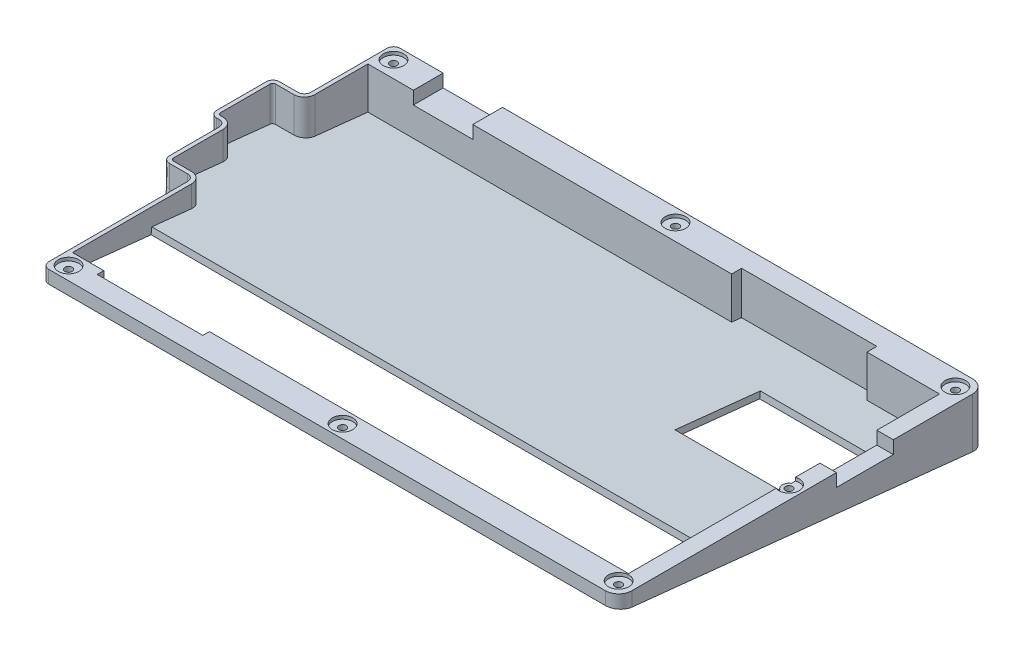
SolidWorks part; units mm, degrees
ref_plane "Front Plane" through (0, 0, 0) normal (0, 0, 1) x (1, 0, 0)
ref_plane "Top Plane" through (0, 0, 0) normal (0, 1, 0) x (1, 0, 0)
ref_plane "Right Plane" through (0, 0, 0) normal (1, 0, 0) x (0, 0, -1)
sketch "Sketch1" plane through (0, 0, 0) normal (0, 1, 0) x (1, 0, 0)
  line L0 (138.4196, 31.7518) -> (125.4196, 31.7518)
  line L1 (-35.0204, 31.7518) -> (107.4196, 31.7518)
  line L2 (140.4196, 29.7518) -> (140.4196, 6.7018)
  line L3 (-34.0204, 3.7518) -> (-34.0204, 22.7518)
  line L4 (136.4596, 27.7518) -> (136.4396, 27.7518)
  line L5 (142.4196, 4.7018) -> (147.9496, 4.7018)
  line L6 (-34.0204, 22.7518) -> (-12.0204, 22.7518)
  line L8 (149.9496, 2.7018) -> (149.9496, -12.3482)
  line L11 (147.9496, -14.3482) -> (147.1896, -14.3482)
  line L14 (145.1896, -16.3482) -> (145.1896, -31.3982)
  line L17 (143.1896, -33.3982) -> (137.6696, -33.3982)
  line L20 (135.6696, -35.3982) -> (135.6696, -77.4982)
  line L21 (-34.0204, -25.6003) -> (-34.0204, -71.4982)
  line L23 (133.6696, -79.4982) -> (-35.0204, -79.4982)
  line L28 (-39.0204, 27.7518) -> (-39.0204, 3.7518)
  line L31 (-34.0204, 3.7518) -> (-39.0204, 3.7518)
  line L32 (-34.0204, -13.4982) -> (-39.0204, -13.4982)
  line L33 (-39.0204, -75.4982) -> (-39.0204, -13.4982)
  line L34 (-34.0204, -71.4982) -> (92.9796, -71.4982)
  line L35 (92.9796, -71.4982) -> (92.9796, -73.4982)
  line L36 (92.9796, -73.4982) -> (124.9796, -73.4982)
  line L37 (124.9796, -73.4982) -> (124.9796, -71.4982)
  line L39 (134.4706, -35.3982) -> (134.4706, -71.4982)
  line L40 (134.4706, -71.4982) -> (124.9796, -71.4982)
  line L41 (137.6696, -32.1992) -> (143.1896, -32.1992)
  line L42 (-34.0204, -13.4982) -> (-34.0204, -22.1362)
  line L43 (143.9906, -31.3982) -> (143.9906, -16.3482)
  line L44 (-12.0204, 22.7518) -> (-12.0204, 25.7518)
  line L45 (147.1896, -13.1492) -> (147.9496, -13.1492)
  line L46 (148.7506, -12.3482) -> (148.7506, 2.7018)
  line L47 (-12.0204, 25.7518) -> (28.9796, 25.7518)
  line L48 (28.9796, 25.7518) -> (28.9796, 22.7518)
  line L49 (28.9796, 22.7518) -> (107.4196, 22.7518)
  line L50 (147.9496, 3.5027) -> (142.4196, 3.5027)
  line L51 (107.4196, 22.7518) -> (107.4196, 31.7518)
  line L52 (139.2206, 6.7018) -> (139.2206, 22.7518)
  line L53 (125.4196, 31.7518) -> (125.4196, 22.7518)
  line L54 (139.2206, 22.7518) -> (125.4196, 22.7518)
  arc A0 (138.4196, 31.7518) -> (140.4196, 29.7518) centre (138.4196, 29.7518) cw
  arc A1 (140.4196, 6.7018) -> (142.4196, 4.7018) centre (142.4196, 6.7018) ccw
  arc A2 (149.9496, 2.7018) -> (147.9496, 4.7018) centre (147.9496, 2.7018) ccw
  arc A3 (149.9496, -12.3482) -> (147.9496, -14.3482) centre (147.9496, -12.3482) cw
  arc A4 (147.1896, -14.3482) -> (145.1896, -16.3482) centre (147.1896, -16.3482) ccw
  arc A5 (145.1896, -31.3982) -> (143.1896, -33.3982) centre (143.1896, -31.3982) cw
  arc A6 (-35.0204, 31.7518) -> (-39.0204, 27.7518) centre (-35.0204, 27.7518) ccw
  arc A7 (-39.0204, -75.4982) -> (-35.0204, -79.4982) centre (-35.0204, -75.4982) ccw
  arc A8 (133.6696, -79.4982) -> (135.6696, -77.4982) centre (133.6696, -77.4982) ccw
  arc A9 (135.6696, -35.3982) -> (137.6696, -33.3982) centre (137.6696, -35.3982) cw
  circle A10 centre (-34.4204, 27.1518) radius 1.1
  circle A11 centre (51.0096, 27.7518) radius 1.1
  circle A12 centre (136.4396, 27.7518) radius 1.1
  circle A13 centre (-34.4204, -74.8982) radius 1.1
  circle A14 centre (48.6296, -75.4982) radius 1.1
  circle A15 centre (131.6496, -75.4982) radius 1.1
  circle A16 centre (-35.0204, -23.8682) radius 1.1
  arc A27 (-34.0204, -22.1362) -> (-34.0204, -25.6003) centre (-35.0204, -23.8682) cw
  arc A28 (139.2206, 6.7018) -> (142.4196, 3.5027) centre (142.4196, 6.7018) ccw
  arc A29 (147.9496, 3.5027) -> (148.7506, 2.7018) centre (147.9496, 2.7018) cw
  arc A30 (148.7506, -12.3482) -> (147.9496, -13.1492) centre (147.9496, -12.3482) cw
  arc A31 (147.1896, -13.1492) -> (143.9906, -16.3482) centre (147.1896, -16.3482) ccw
  arc A32 (143.9906, -31.3982) -> (143.1896, -32.1992) centre (143.1896, -31.3982) cw
  arc A33 (137.6696, -32.1992) -> (134.4706, -35.3982) centre (137.6696, -35.3982) ccw
extrude "Boss-Extrude2" add sketch "Sketch1" against normal blind 4.7 contours L41 A33 L39 L40 L37 L36 L35 L34 L21 A27 L42 L32 L33 A7 L23 A8 L20 A9 L17 A5 L14 A4 L11 A3 L8 A2 L5 A1 L2 A0 L0 L53 L54 L52 A28 L50 A29 L46 A30 L45 A31 L43 A32 A12 A13 A14 A15 | L1 A6 L28 L31 L3 L6 L44 L47 L48 L49 L51 A11 A10 region at (138.2833, 0, -29.6154) region at (31.7683, 0, -26.4895)
move or copy body "Body-Move/Copy1" bodies to move or copy 105 104 copy no rotation origin (55.4646, -2.35, 0) rotation axis (0, 0, 1) rotation angle 180
sketch "Sketch3" plane through (149.9496, 0, 0) normal (1, 0, 0) x (0, 0, -1)
  line L0 (-79.4982, 0) -> (-79.4982, -4.7) construction
  line L1 (-79.4982, 0) -> (-79.4982, -4.7)
  line L2 (31.7518, 0) -> (31.7518, -4.7) construction
  line L3 (31.7518, 0) -> (31.7518, -4.7)
  line L5 (-79.4982, -4.7) -> (31.7518, -16.3928)
  line L6 (31.7518, -16.3928) -> (31.7518, -4.7)
  line L7 (31.7518, -4.7) -> (-79.4982, -4.7)
  line M3 (-75.4982, -4.7) -> (-13.4982, -4.7)
  dimension "D1" = 6
extrude "Boss-Extrude3" add sketch "Sketch3" against normal up to surface (188.97 mm away) contours L6 L7 L5 M3 region at (149.9496, -8.5976, 5.3315) up to face at (-39.0204, -2.35, 4.8232)
sketch "Sketch4" plane through (0, -4.7, 0) normal (0, 1, 0) x (1, 0, 0)
  line L2 (145.9496, -79.4982) -> (149.9496, -79.4982)
  line L3 (149.9496, -79.4982) -> (149.9496, -75.4982)
  line L4 (-29.4904, 6.7018) -> (-29.4904, 29.7518)
  line L5 (-27.4904, 31.7518) -> (-39.0204, 31.7518)
  line L6 (-36.2604, -14.3482) -> (-37.0204, -14.3482)
  line L7 (-39.0204, -12.3482) -> (-39.0204, -79.4982)
  line L8 (-39.0204, -79.4982) -> (-22.7404, -79.4982)
  line L9 (-24.7404, -77.4982) -> (-24.7404, -35.3982)
  line L10 (-26.7404, -33.3982) -> (-32.2604, -33.3982)
  line L11 (-34.2604, -31.3982) -> (-34.2604, -16.3482)
  line L12 (-36.2604, -14.3482) -> (-37.0204, -14.3482)
  line L13 (-39.0204, -12.3482) -> (-39.0204, -79.4982)
  line L14 (-39.0204, -79.4982) -> (-22.7404, -79.4982)
  line L15 (-24.7404, -77.4982) -> (-24.7404, -35.3982)
  line L16 (-26.7404, -33.3982) -> (-32.2604, -33.3982)
  line L17 (-34.2604, -31.3982) -> (-34.2604, -16.3482)
  line L18 (-39.0204, 31.7518) -> (-39.0204, 2.7018)
  line L19 (-37.0204, 4.7018) -> (-31.4904, 4.7018)
  line L20 (-29.4904, 6.7018) -> (-29.4904, 29.7518)
  line L21 (-27.4904, 31.7518) -> (-39.0204, 31.7518)
  line L22 (-39.0204, 31.7518) -> (-39.0204, 2.7018)
  line L23 (-37.0204, 4.7018) -> (-31.4904, 4.7018)
  line L24 (145.9496, -79.4982) -> (149.9496, -79.4982)
  line L25 (149.9496, -79.4982) -> (149.9496, -75.4982)
  line L26 (149.9496, 31.7518) -> (145.9496, 31.7518)
  line L27 (149.9496, 27.7518) -> (149.9496, 31.7518)
  line L28 (149.9496, 31.7518) -> (145.9496, 31.7518)
  line L29 (149.9496, 27.7518) -> (149.9496, 31.7518)
  arc A1 (145.9496, -79.4982) -> (149.9496, -75.4982) centre (145.9496, -75.4982) ccw
  arc A2 (145.9496, -79.4982) -> (149.9496, -75.4982) centre (145.9496, -75.4982) ccw
  arc A3 (-27.4904, 31.7518) -> (-29.4904, 29.7518) centre (-27.4904, 29.7518) ccw
  arc A4 (-37.0204, 4.7018) -> (-39.0204, 2.7018) centre (-37.0204, 2.7018) ccw
  arc A5 (-39.0204, -12.3482) -> (-37.0204, -14.3482) centre (-37.0204, -12.3482) ccw
  arc A6 (-24.7404, -77.4982) -> (-22.7404, -79.4982) centre (-22.7404, -77.4982) ccw
  arc A7 (-24.7404, -35.3982) -> (-26.7404, -33.3982) centre (-26.7404, -35.3982) ccw
  arc A8 (-34.2604, -31.3982) -> (-32.2604, -33.3982) centre (-32.2604, -31.3982) ccw
  arc A9 (-34.2604, -16.3482) -> (-36.2604, -14.3482) centre (-36.2604, -16.3482) ccw
  arc A10 (-39.0204, -12.3482) -> (-37.0204, -14.3482) centre (-37.0204, -12.3482) ccw
  arc A11 (-24.7404, -77.4982) -> (-22.7404, -79.4982) centre (-22.7404, -77.4982) ccw
  arc A12 (-24.7404, -35.3982) -> (-26.7404, -33.3982) centre (-26.7404, -35.3982) ccw
  arc A13 (-34.2604, -31.3982) -> (-32.2604, -33.3982) centre (-32.2604, -31.3982) ccw
  arc A14 (-34.2604, -16.3482) -> (-36.2604, -14.3482) centre (-36.2604, -16.3482) ccw
  arc A15 (-31.4904, 4.7018) -> (-29.4904, 6.7018) centre (-31.4904, 6.7018) ccw
  arc A16 (-27.4904, 31.7518) -> (-29.4904, 29.7518) centre (-27.4904, 29.7518) ccw
  arc A17 (-37.0204, 4.7018) -> (-39.0204, 2.7018) centre (-37.0204, 2.7018) ccw
  arc A18 (-31.4904, 4.7018) -> (-29.4904, 6.7018) centre (-31.4904, 6.7018) ccw
  arc A19 (149.9496, 27.7518) -> (145.9496, 31.7518) centre (145.9496, 27.7518) ccw
  arc A20 (149.9496, 27.7518) -> (145.9496, 31.7518) centre (145.9496, 27.7518) ccw
  dimension "D1" = 0
  dimension "D2" = 0
  dimension "D3" = 0
  dimension "D4" = 0
extrude "Cut-Extrude1" cut sketch "Sketch4" against normal through all
ref_plane "Plane4" through (0, 15, 0) normal (0, 1, 0) x (1, 0, 0)
sketch "Sketch10" plane through (0, 15, 0) normal (0, 1, 0) x (1, 0, 0)
  line L0 (-14.4904, 22.7518) -> (3.5096, 22.7518)
  line L1 (144.9496, 3.7518) -> (144.9496, -13.4982)
  line L27 (-14.4904, 31.7518) -> (-14.4904, 22.7518)
  line L28 (-14.4904, 22.7518) -> (-28.2913, 22.7518)
  line L29 (-28.2913, 22.7518) -> (-28.2913, 6.7018)
  line L30 (-31.4904, 3.5027) -> (-37.0204, 3.5027)
  line L31 (-37.8213, 2.7018) -> (-37.8213, -12.3482)
  line L32 (-37.0204, -13.1492) -> (-36.2604, -13.1492)
  line L33 (-33.0613, -16.3482) -> (-33.0613, -31.3982)
  line L34 (-32.2604, -32.1992) -> (-26.7404, -32.1992)
  line L35 (-23.5413, -35.3982) -> (-23.5413, -71.4982)
  line L36 (-23.5413, -71.4982) -> (-14.0504, -71.4982)
  line L37 (-14.0504, -71.4982) -> (-14.0504, -73.4982)
  line L38 (-14.0504, -73.4982) -> (17.9496, -73.4982)
  line L39 (17.9496, -73.4982) -> (17.9496, -71.4982)
  line L40 (17.9496, -71.4982) -> (144.9496, -71.4982)
  line L41 (144.9496, -71.4982) -> (144.9496, -25.6003)
  line L42 (144.9496, -22.1362) -> (144.9496, -13.4982)
  line L43 (144.9496, -13.4982) -> (149.9496, -13.4982)
  line L44 (149.9496, -13.4982) -> (149.9496, 3.7518)
  line L45 (149.9496, 3.7518) -> (144.9496, 3.7518)
  line L46 (144.9496, 3.7518) -> (144.9496, 22.7518)
  line L47 (144.9496, 22.7518) -> (122.9496, 22.7518)
  line L48 (122.9496, 22.7518) -> (122.9496, 25.7518)
  line L49 (122.9496, 25.7518) -> (81.9496, 25.7518)
  line L50 (81.9496, 25.7518) -> (81.9496, 22.7518)
  line L51 (81.9496, 22.7518) -> (3.5096, 22.7518)
  line L52 (3.5096, 22.7518) -> (3.5096, 31.7518)
  line L53 (3.5096, 31.7518) -> (-14.4904, 31.7518)
  line L54 (-14.4904, 31.7518) -> (-14.4904, 22.7518)
  line L55 (-14.4904, 22.7518) -> (-28.2913, 22.7518)
  line L56 (-28.2913, 22.7518) -> (-28.2913, 6.7018)
  line L57 (-31.4904, 3.5027) -> (-37.0204, 3.5027)
  line L58 (-37.8213, 2.7018) -> (-37.8213, -12.3482)
  line L59 (-37.0204, -13.1492) -> (-36.2604, -13.1492)
  line L60 (-33.0613, -16.3482) -> (-33.0613, -31.3982)
  line L61 (-32.2604, -32.1992) -> (-26.7404, -32.1992)
  line L62 (-23.5413, -35.3982) -> (-23.5413, -71.4982)
  line L63 (-23.5413, -71.4982) -> (-14.0504, -71.4982)
  line L64 (-14.0504, -71.4982) -> (-14.0504, -73.4982)
  line L65 (-14.0504, -73.4982) -> (17.9496, -73.4982)
  line L66 (17.9496, -73.4982) -> (17.9496, -71.4982)
  line L67 (17.9496, -71.4982) -> (144.9496, -71.4982)
  line L68 (144.9496, -71.4982) -> (144.9496, -25.6003)
  line L69 (144.9496, -22.1362) -> (144.9496, -13.4982)
  line L70 (144.9496, -13.4982) -> (149.9496, -13.4982)
  line L71 (149.9496, -13.4982) -> (149.9496, 3.7518)
  line L72 (149.9496, 3.7518) -> (144.9496, 3.7518)
  line L73 (144.9496, 3.7518) -> (144.9496, 22.7518)
  line L74 (144.9496, 22.7518) -> (122.9496, 22.7518)
  line L75 (122.9496, 22.7518) -> (122.9496, 25.7518)
  line L76 (122.9496, 25.7518) -> (81.9496, 25.7518)
  line L77 (81.9496, 25.7518) -> (81.9496, 22.7518)
  line L78 (81.9496, 22.7518) -> (3.5096, 22.7518)
  line L79 (3.5096, 22.7518) -> (3.5096, 31.7518)
  line L80 (3.5096, 31.7518) -> (-14.4904, 31.7518)
  arc A7 (-31.4904, 3.5027) -> (-28.2913, 6.7018) centre (-31.4904, 6.7018) ccw
  arc A8 (-37.0204, 3.5027) -> (-37.8213, 2.7018) centre (-37.0204, 2.7018) ccw
  arc A9 (-37.8213, -12.3482) -> (-37.0204, -13.1492) centre (-37.0204, -12.3482) ccw
  arc A10 (-33.0613, -16.3482) -> (-36.2604, -13.1492) centre (-36.2604, -16.3482) ccw
  arc A11 (-33.0613, -31.3982) -> (-32.2604, -32.1992) centre (-32.2604, -31.3982) ccw
  arc A12 (-23.5413, -35.3982) -> (-26.7404, -32.1992) centre (-26.7404, -35.3982) ccw
  arc A13 (144.9496, -22.1362) -> (144.9496, -25.6003) centre (145.9496, -23.8682) ccw
  arc A14 (-31.4904, 3.5027) -> (-28.2913, 6.7018) centre (-31.4904, 6.7018) ccw
  arc A15 (-37.0204, 3.5027) -> (-37.8213, 2.7018) centre (-37.0204, 2.7018) ccw
  arc A16 (-37.8213, -12.3482) -> (-37.0204, -13.1492) centre (-37.0204, -12.3482) ccw
  arc A17 (-33.0613, -16.3482) -> (-36.2604, -13.1492) centre (-36.2604, -16.3482) ccw
  arc A18 (-33.0613, -31.3982) -> (-32.2604, -32.1992) centre (-32.2604, -31.3982) ccw
  arc A19 (-23.5413, -35.3982) -> (-26.7404, -32.1992) centre (-26.7404, -35.3982) ccw
  arc A20 (144.9496, -22.1362) -> (144.9496, -25.6003) centre (145.9496, -23.8682) ccw
  dimension "D1" = 0
extrude "Cut-Extrude2" cut sketch "Sketch10" against normal through all contours A20 L69 L1 L73 L74 L75 L76 L77 L78 L0 L55 L56 A14 L57 A15 L58 A16 L59 A17 L60 A18 L61 A19 L62 L63 L64 L65 L66 L67 L68 region at (57.9798, 15, 23.6888)
sketch "Sketch11" plane through (144.9496, 0, 0) normal (-1, 0, 0) x (0, 0, 1)
  line L0 (-22.7518, -15.4469) -> (71.4982, -5.5408)
  line L1 (71.4982, -5.5408) -> (71.4982, -3.5408)
  line L2 (71.4982, 0) -> (71.4982, -5.5408) construction
  line L3 (71.4982, -3.5408) -> (-22.7518, -13.4469)
  line L4 (-22.7518, 0) -> (-22.7518, -15.4469) construction
  line L5 (-22.7518, -13.4469) -> (-22.7518, -15.4469)
  dimension "D1" = 2
  dimension "D2" = 2
extrude "Boss-Extrude4" add sketch "Sketch11" along normal up to surface (182.7709 mm away)
sketch "Sketch12" plane through (0, -10.9348, 1.1493) normal (0, 0.9945, -0.1045) x (1, 0, 0)
  line L0 (-29.4904, 7.8943) -> (-29.4904, 24.0327) construction
  line L1 (-29.4904, 24.0327) -> (-37.8213, 24.0327) construction
  line L2 (-37.8213, 24.0327) -> (-37.8213, 5.715) construction
  line L3 (-37.0204, 5.8833) -> (-31.4904, 5.8833) construction
  line L4 (-36.2604, -13.2716) -> (-37.0204, -13.2716) construction
  line L5 (-37.8213, -13.1033) -> (-37.8213, -70.7364) construction
  line L6 (-37.8213, -70.7364) -> (-24.7404, -70.7364) construction
  line L7 (-24.7404, -70.7364) -> (-24.7404, -34.4376) construction
  line L8 (-26.7404, -32.4266) -> (-32.2604, -32.4266) construction
  line L9 (-34.2604, -30.4155) -> (-34.2604, -15.2826) construction
  line L10 (-29.4904, 7.8943) -> (-29.4904, 24.0327)
  line L11 (-29.4904, 24.0327) -> (-37.8213, 24.0327)
  line L12 (-37.8213, 24.0327) -> (-37.8213, 5.715)
  line L13 (-37.0204, 5.8833) -> (-31.4904, 5.8833)
  line L14 (-36.2604, -13.2716) -> (-37.0204, -13.2716)
  line L15 (-37.8213, -13.1033) -> (-37.8213, -70.7364)
  line L16 (-37.8213, -70.7364) -> (-24.7404, -70.7364)
  line L17 (-24.7404, -70.7364) -> (-24.7404, -34.4376)
  line L18 (-26.7404, -32.4266) -> (-32.2604, -32.4266)
  line L19 (-34.2604, -30.4155) -> (-34.2604, -15.2826)
  line L20 (-37.8213, 24.0327) -> (-37.8213, 25.9101)
  line L21 (-29.4904, 24.0327) -> (-29.4904, 27.1127)
  line L22 (-29.4904, 27.1127) -> (-37.8213, 25.9101)
  ellipse E0 centre (-31.4904, 7.8943) end of major axis (-31.4904, 9.9053) minor radius 2 (-31.4904, 5.8833) -> (-29.4904, 7.8943) ccw construction
  ellipse E1 centre (-37.0204, 3.8723) end of major axis (-37.0204, 5.8833) minor radius 2 (-37.0204, 5.8833) -> (-37.8213, 5.715) ccw construction
  ellipse E2 centre (-37.0204, -11.2606) end of major axis (-37.0204, -9.2496) minor radius 2 (-37.8213, -13.1033) -> (-37.0204, -13.2716) ccw construction
  ellipse E3 centre (-26.7404, -34.4376) end of major axis (-26.7404, -32.4266) minor radius 2 (-24.7404, -34.4376) -> (-26.7404, -32.4266) ccw construction
  ellipse E4 centre (-32.2604, -30.4155) end of major axis (-32.2604, -28.4045) minor radius 2 (-34.2604, -30.4155) -> (-32.2604, -32.4266) ccw construction
  ellipse E5 centre (-36.2604, -15.2826) end of major axis (-36.2604, -13.2716) minor radius 2 (-34.2604, -15.2826) -> (-36.2604, -13.2716) ccw construction
  ellipse E6 centre (-31.4904, 7.8943) end of major axis (-31.4904, 9.9053) minor radius 2 (-31.4904, 5.8833) -> (-29.4904, 7.8943) ccw
  ellipse E7 centre (-37.0204, 3.8723) end of major axis (-37.0204, 5.8833) minor radius 2 (-37.0204, 5.8833) -> (-37.8213, 5.715) ccw
  ellipse E8 centre (-37.0204, -11.2606) end of major axis (-37.0204, -9.2496) minor radius 2 (-37.8213, -13.1033) -> (-37.0204, -13.2716) ccw
  ellipse E9 centre (-26.7404, -34.4376) end of major axis (-26.7404, -32.4266) minor radius 2 (-24.7404, -34.4376) -> (-26.7404, -32.4266) ccw
  ellipse E10 centre (-32.2604, -30.4155) end of major axis (-32.2604, -28.4045) minor radius 2 (-34.2604, -30.4155) -> (-32.2604, -32.4266) ccw
  ellipse E11 centre (-36.2604, -15.2826) end of major axis (-36.2604, -13.2716) minor radius 2 (-34.2604, -15.2826) -> (-36.2604, -13.2716) ccw
sketch "Sketch26" plane through (-37.8213, 0, 0) normal (-1, 0, 0) x (0, 0, 1)
  line L0 (14.1808, -9.5651) -> (-4.5344, -11.5322)
  line L1 (-4.5344, -13.5322) -> (14.1808, -11.5651)
  line L4 (-22.7518, -15.4469) -> (-4.5344, -13.5322)
  line L5 (-4.5344, -13.5322) -> (-4.5344, -11.5322)
  line L6 (-4.5344, -11.5322) -> (-22.7518, -13.4469)
  line L7 (-22.7518, -13.4469) -> (-22.7518, -15.4469)
  line L8 (-22.7518, -15.4469) -> (-4.5344, -13.5322)
  line L9 (-4.5344, -13.5322) -> (-4.5344, -11.5322)
  line L10 (-4.5344, -11.5322) -> (-22.7518, -13.4469)
  line L11 (-22.7518, -13.4469) -> (-22.7518, -15.4469)
  line L12 (14.1808, -9.5651) -> (14.1808, -11.5651)
  line L13 (14.1808, -11.5651) -> (71.4982, -5.5408)
  line L14 (71.4982, -5.5408) -> (71.4982, -3.5408)
  line L15 (71.4982, -3.5408) -> (14.1808, -9.5651)
  line L16 (14.1808, -9.5651) -> (14.1808, -11.5651)
  line L17 (14.1808, -11.5651) -> (71.4982, -5.5408)
  line L18 (71.4982, -5.5408) -> (71.4982, -3.5408)
  line L19 (71.4982, -3.5408) -> (14.1808, -9.5651)
  line M9 (14.1808, -9.5651) -> (14.1808, -11.5651)
  line M10 (14.1808, -11.5651) -> (71.4982, -5.5408)
  line M11 (71.4982, -5.5408) -> (71.4982, -3.5408)
  line M12 (71.4982, -3.5408) -> (14.1808, -9.5651)
  dimension "D1" = 0
  dimension "D2" = 0
extrude "Boss-Extrude10" add sketch "Sketch26" along normal blind 11 contours L10 L11 L8 L9 | L9 L1 L0 M9 | M12 M9 M10 M11 region at (-37.8213, -11.5487, 4.8232) region at (-37.8213, -7.553, 42.8395) region at (-37.8213, -13.4895, -13.6431)
sketch "Sketch28" plane through (0, -10.9348, 1.1493) normal (0, 0.9945, -0.1045) x (1, 0, 0)
  line L0 (-48.8213, 24.0327) -> (-52.7132, 28.3929)
  line L1 (-52.7132, 28.3929) -> (-29.4904, 30.8021)
  line L2 (-29.4904, 30.8021) -> (-29.4904, 24.0327)
  line L10 (-29.4904, 7.8943) -> (-29.4904, 24.0327)
  line L11 (-29.4904, 24.0327) -> (-48.8213, 24.0327)
  line L12 (-48.8213, 24.0327) -> (-48.8213, -70.7364)
  line L13 (-48.8213, -70.7364) -> (-24.7404, -70.7364)
  line L14 (-24.7404, -70.7364) -> (-24.7404, -34.4376)
  line L15 (-26.7404, -32.4266) -> (-32.2604, -32.4266)
  line L16 (-34.2604, -30.4155) -> (-34.2604, -15.2826)
  line L17 (-36.2604, -13.2716) -> (-37.0204, -13.2716)
  line L18 (-39.0204, -11.2606) -> (-39.0204, 3.8723)
  line L19 (-37.0204, 5.8833) -> (-31.4904, 5.8833)
  line L20 (-29.4904, 7.8943) -> (-29.4904, 24.0327)
  line L21 (-29.4904, 24.0327) -> (-48.8213, 24.0327)
  line L22 (-48.8213, 24.0327) -> (-48.8213, -70.7364)
  line L23 (-48.8213, -70.7364) -> (-24.7404, -70.7364)
  line L24 (-24.7404, -70.7364) -> (-24.7404, -34.4376)
  line L25 (-26.7404, -32.4266) -> (-32.2604, -32.4266)
  line L26 (-34.2604, -30.4155) -> (-34.2604, -15.2826)
  line L27 (-36.2604, -13.2716) -> (-37.0204, -13.2716)
  line L28 (-39.0204, -11.2606) -> (-39.0204, 3.8723)
  line L29 (-37.0204, 5.8833) -> (-31.4904, 5.8833)
  ellipse E6 centre (-31.4904, 7.8943) end of major axis (-31.4904, 9.9053) minor radius 2 (-31.4904, 5.8833) -> (-29.4904, 7.8943) ccw
  ellipse E7 centre (-26.7404, -34.4376) end of major axis (-26.7404, -32.4266) minor radius 2 (-24.7404, -34.4376) -> (-26.7404, -32.4266) ccw
  ellipse E8 centre (-32.2604, -30.4155) end of major axis (-32.2604, -28.4045) minor radius 2 (-34.2604, -30.4155) -> (-32.2604, -32.4266) ccw
  ellipse E9 centre (-36.2604, -15.2826) end of major axis (-36.2604, -13.2716) minor radius 2 (-34.2604, -15.2826) -> (-36.2604, -13.2716) ccw
  ellipse E10 centre (-37.0204, -11.2606) end of major axis (-37.0204, -9.2496) minor radius 2 (-39.0204, -11.2606) -> (-37.0204, -13.2716) ccw
  ellipse E11 centre (-37.0204, 3.8723) end of major axis (-37.0204, 5.8833) minor radius 2 (-37.0204, 5.8833) -> (-39.0204, 3.8723) ccw
  ellipse E12 centre (-31.4904, 7.8943) end of major axis (-31.4904, 9.9053) minor radius 2 (-31.4904, 5.8833) -> (-29.4904, 7.8943) ccw
  ellipse E13 centre (-26.7404, -34.4376) end of major axis (-26.7404, -32.4266) minor radius 2 (-24.7404, -34.4376) -> (-26.7404, -32.4266) ccw
  ellipse E14 centre (-32.2604, -30.4155) end of major axis (-32.2604, -28.4045) minor radius 2 (-34.2604, -30.4155) -> (-32.2604, -32.4266) ccw
  ellipse E15 centre (-36.2604, -15.2826) end of major axis (-36.2604, -13.2716) minor radius 2 (-34.2604, -15.2826) -> (-36.2604, -13.2716) ccw
  ellipse E16 centre (-37.0204, -11.2606) end of major axis (-37.0204, -9.2496) minor radius 2 (-39.0204, -11.2606) -> (-37.0204, -13.2716) ccw
  ellipse E17 centre (-37.0204, 3.8723) end of major axis (-37.0204, 5.8833) minor radius 2 (-37.0204, 5.8833) -> (-39.0204, 3.8723) ccw
  ellipse M17 centre (-31.4904, 7.8943) end of major axis (-31.4904, 9.9053) minor radius 2 (-31.4904, 5.8833) -> (-29.4904, 7.8943) ccw
  line M18 (-29.4904, 7.8943) -> (-29.4904, 24.0327)
  line M19 (-29.4904, 24.0327) -> (-48.8213, 24.0327)
  line M20 (-48.8213, 24.0327) -> (-48.8213, -70.7364)
  line M21 (-48.8213, -70.7364) -> (-24.7404, -70.7364)
  line M22 (-24.7404, -70.7364) -> (-24.7404, -34.4376)
  ellipse M23 centre (-26.7404, -34.4376) end of major axis (-26.7404, -32.4266) minor radius 2 (-24.7404, -34.4376) -> (-26.7404, -32.4266) ccw
  line M24 (-26.7404, -32.4266) -> (-32.2604, -32.4266)
  ellipse M25 centre (-32.2604, -30.4155) end of major axis (-32.2604, -28.4045) minor radius 2 (-32.2604, -32.4266) -> (-34.2604, -30.4155) cw
  line M26 (-34.2604, -30.4155) -> (-34.2604, -15.2826)
  ellipse M27 centre (-36.2604, -15.2826) end of major axis (-36.2604, -13.2716) minor radius 2 (-34.2604, -15.2826) -> (-36.2604, -13.2716) ccw
  line M28 (-36.2604, -13.2716) -> (-37.0204, -13.2716)
  ellipse M29 centre (-37.0204, -11.2606) end of major axis (-37.0204, -9.2496) minor radius 2 (-37.0204, -13.2716) -> (-39.0204, -11.2606) cw
  line M30 (-39.0204, -11.2606) -> (-39.0204, 3.8723)
  ellipse M31 centre (-37.0204, 3.8723) end of major axis (-37.0204, 5.8833) minor radius 2 (-39.0204, 3.8723) -> (-37.0204, 5.8833) cw
  line M32 (-37.0204, 5.8833) -> (-31.4904, 5.8833)
  dimension "D1" = 0
extrude "Cut-Extrude8" cut sketch "Sketch28" against normal blind 11 contours M32 M17 M18 M19 M20 M21 M22 M23 M24 M25 M26 M27 M28 M29 M30 M31 | L2 L1 L0 M19 region at (-39.4803, -13.7524, -25.6581) region at (-38.8035, -7.967, 29.3861)
sketch "Sketch30" plane through (122.9496, 0, 0) normal (-1, 0, 0) x (0, 0, 1)
  line L0 (-25.7518, -15.7622) -> (-22.7518, -15.4469)
  line L1 (-22.7518, -15.4469) -> (-22.7518, -13.4469)
  line L2 (-22.7518, -15.4469) -> (-22.7518, -13.4469) construction
  line L3 (-22.7518, -13.4469) -> (-25.7518, -13.7622)
  line L4 (-25.7518, 0) -> (-25.7518, -15.7622) construction
  line L5 (-25.7518, -13.7622) -> (-25.7518, -15.7622)
extrude "Boss-Extrude11" add sketch "Sketch30" along normal up to surface (41 mm away)
sketch "Sketch32" plane through (17.9496, 0, 0) normal (-1, 0, 0) x (0, 0, 1)
  line L0 (73.4982, -5.3306) -> (71.4982, -5.5408)
  line L1 (71.4982, -5.5408) -> (71.4982, -3.5408)
  line L2 (71.4982, -3.5408) -> (73.4982, -3.3306)
  line L3 (73.4982, 0) -> (73.4982, -5.3306) construction
  line L4 (73.4982, -3.3306) -> (73.4982, -5.3306)
  dimension "D1" = 2
extrude "Boss-Extrude14" add sketch "Sketch32" along normal up to surface (32 mm away)
sketch "Sketch35" plane through (0, 0, 0) normal (0, 1, 0) x (1, 0, 0)
  line L0 (149.9496, 3.7518) -> (149.9496, -13.4982)
  line L1 (149.9496, -13.4982) -> (144.9496, -13.4982)
  line L2 (144.9496, -13.4982) -> (144.9496, 3.7518)
  line L3 (144.9496, 3.7518) -> (149.9496, 3.7518)
ref_plane "Plane5" through (149.9496, -5.1204, 75.4982) normal (0, -1, 0) x (-1, 0, 0)
sketch "Sketch47" plane through (0, 0, 0) normal (0, 1, 0) x (1, 0, 0)
  circle A0 centre (145.3496, -74.8982) radius 3.1
  circle A1 centre (62.2996, -75.4982) radius 3.1
  circle A2 centre (-20.7204, -75.4982) radius 3.1
  circle A3 centre (-25.5104, 27.7518) radius 3.1
  circle A4 centre (59.9196, 27.7518) radius 3.1
  circle A5 centre (145.3496, 27.1518) radius 3.1
  circle A6 centre (145.9496, -23.8682) radius 3.1
extrude "Cut-Extrude17" cut sketch "Sketch47" against normal blind 1.8
sketch "Sketch48" plane through (0, 0, 0) normal (0, 1, 0) x (1, 0, 0)
  line L10 (145.9496, 31.7518) -> (3.5096, 31.7518)
  line L11 (3.5096, 31.7518) -> (3.5096, 22.7518)
  line L12 (3.5096, 22.7518) -> (81.9496, 22.7518)
  line L13 (81.9496, 22.7518) -> (81.9496, 25.7518)
  line L14 (81.9496, 25.7518) -> (122.9496, 25.7518)
  line L15 (122.9496, 25.7518) -> (122.9496, 22.7518)
  line L16 (122.9496, 22.7518) -> (144.9496, 22.7518)
  line L17 (144.9496, 22.7518) -> (144.9496, 3.7518)
  line L18 (144.9496, 3.7518) -> (149.9496, 3.7518)
  line L19 (149.9496, 3.7518) -> (149.9496, 27.7518)
  line L20 (145.9496, 31.7518) -> (3.5096, 31.7518)
  line L21 (3.5096, 31.7518) -> (3.5096, 22.7518)
  line L22 (3.5096, 22.7518) -> (81.9496, 22.7518)
  line L23 (81.9496, 22.7518) -> (81.9496, 25.7518)
  line L24 (81.9496, 25.7518) -> (122.9496, 25.7518)
  line L25 (122.9496, 25.7518) -> (122.9496, 22.7518)
  line L26 (122.9496, 22.7518) -> (144.9496, 22.7518)
  line L27 (144.9496, 22.7518) -> (144.9496, 3.7518)
  line L28 (144.9496, 3.7518) -> (149.9496, 3.7518)
  line L29 (149.9496, 3.7518) -> (149.9496, 27.7518)
  line L47 (144.9496, -13.4982) -> (144.9496, -20.9339)
  line L48 (144.9496, -26.8025) -> (144.9496, -71.4982)
  line L49 (144.9496, -71.4982) -> (17.9496, -71.4982)
  line L50 (17.9496, -71.4982) -> (17.9496, -73.4982)
  line L51 (17.9496, -73.4982) -> (-14.0504, -73.4982)
  line L52 (-14.0504, -73.4982) -> (-14.0504, -71.4982)
  line L53 (-14.0504, -71.4982) -> (-23.5413, -71.4982)
  line L54 (-23.5413, -71.4982) -> (-23.5413, -35.3982)
  line L55 (-26.7404, -32.1992) -> (-32.2604, -32.1992)
  line L56 (-33.0613, -31.3982) -> (-33.0613, -16.3482)
  line L57 (-36.2604, -13.1492) -> (-37.0204, -13.1492)
  line L58 (-37.8213, -12.3482) -> (-37.8213, 2.7018)
  line L59 (-37.0204, 3.5027) -> (-31.4904, 3.5027)
  line L60 (-28.2913, 6.7018) -> (-28.2913, 22.7518)
  line L61 (-28.2913, 22.7518) -> (-14.4904, 22.7518)
  line L62 (-14.4904, 22.7518) -> (-14.4904, 31.7518)
  line L63 (-14.4904, 31.7518) -> (-27.4904, 31.7518)
  line L64 (-29.4904, 29.7518) -> (-29.4904, 6.7018)
  line L65 (-31.4904, 4.7018) -> (-37.0204, 4.7018)
  line L66 (-39.0204, 2.7018) -> (-39.0204, -12.3482)
  line L67 (-37.0204, -14.3482) -> (-36.2604, -14.3482)
  line L68 (-34.2604, -16.3482) -> (-34.2604, -31.3982)
  line L69 (-32.2604, -33.3982) -> (-26.7404, -33.3982)
  line L70 (-24.7404, -35.3982) -> (-24.7404, -77.4982)
  line L71 (-22.7404, -79.4982) -> (145.9496, -79.4982)
  line L72 (149.9496, -75.4982) -> (149.9496, -13.4982)
  line L73 (149.9496, -13.4982) -> (144.9496, -13.4982)
  line L74 (144.9496, -13.4982) -> (144.9496, -20.9339)
  line L75 (144.9496, -26.8025) -> (144.9496, -71.4982)
  line L76 (144.9496, -71.4982) -> (17.9496, -71.4982)
  line L77 (17.9496, -71.4982) -> (17.9496, -73.4982)
  line L78 (17.9496, -73.4982) -> (-14.0504, -73.4982)
  line L79 (-14.0504, -73.4982) -> (-14.0504, -71.4982)
  line L80 (-14.0504, -71.4982) -> (-23.5413, -71.4982)
  line L81 (-23.5413, -71.4982) -> (-23.5413, -35.3982)
  line L82 (-26.7404, -32.1992) -> (-32.2604, -32.1992)
  line L83 (-33.0613, -31.3982) -> (-33.0613, -16.3482)
  line L84 (-36.2604, -13.1492) -> (-37.0204, -13.1492)
  line L85 (-37.8213, -12.3482) -> (-37.8213, 2.7018)
  line L86 (-37.0204, 3.5027) -> (-31.4904, 3.5027)
  line L87 (-28.2913, 6.7018) -> (-28.2913, 22.7518)
  line L88 (-28.2913, 22.7518) -> (-14.4904, 22.7518)
  line L89 (-14.4904, 22.7518) -> (-14.4904, 31.7518)
  line L90 (-14.4904, 31.7518) -> (-27.4904, 31.7518)
  line L91 (-29.4904, 29.7518) -> (-29.4904, 6.7018)
  line L92 (-31.4904, 4.7018) -> (-37.0204, 4.7018)
  line L93 (-39.0204, 2.7018) -> (-39.0204, -12.3482)
  line L94 (-37.0204, -14.3482) -> (-36.2604, -14.3482)
  line L95 (-34.2604, -16.3482) -> (-34.2604, -31.3982)
  line L96 (-32.2604, -33.3982) -> (-26.7404, -33.3982)
  line L97 (-24.7404, -35.3982) -> (-24.7404, -77.4982)
  line L98 (-22.7404, -79.4982) -> (145.9496, -79.4982)
  line L99 (149.9496, -75.4982) -> (149.9496, -13.4982)
  line L100 (149.9496, -13.4982) -> (144.9496, -13.4982)
  arc A1 (149.9496, 27.7518) -> (145.9496, 31.7518) centre (145.9496, 27.7518) ccw
  arc A2 (149.9496, 27.7518) -> (145.9496, 31.7518) centre (145.9496, 27.7518) ccw
  arc A18 (144.9496, -26.8025) -> (144.9496, -20.9339) centre (145.9496, -23.8682) ccw
  arc A19 (-23.5413, -35.3982) -> (-26.7404, -32.1992) centre (-26.7404, -35.3982) ccw
  arc A20 (-33.0613, -31.3982) -> (-32.2604, -32.1992) centre (-32.2604, -31.3982) ccw
  arc A21 (-33.0613, -16.3482) -> (-36.2604, -13.1492) centre (-36.2604, -16.3482) ccw
  arc A22 (-37.8213, -12.3482) -> (-37.0204, -13.1492) centre (-37.0204, -12.3482) ccw
  arc A23 (-37.0204, 3.5027) -> (-37.8213, 2.7018) centre (-37.0204, 2.7018) ccw
  arc A24 (-31.4904, 3.5027) -> (-28.2913, 6.7018) centre (-31.4904, 6.7018) ccw
  arc A25 (-27.4904, 31.7518) -> (-29.4904, 29.7518) centre (-27.4904, 29.7518) ccw
  arc A26 (-31.4904, 4.7018) -> (-29.4904, 6.7018) centre (-31.4904, 6.7018) ccw
  arc A27 (-37.0204, 4.7018) -> (-39.0204, 2.7018) centre (-37.0204, 2.7018) ccw
  arc A28 (-39.0204, -12.3482) -> (-37.0204, -14.3482) centre (-37.0204, -12.3482) ccw
  arc A29 (-34.2604, -16.3482) -> (-36.2604, -14.3482) centre (-36.2604, -16.3482) ccw
  arc A30 (-34.2604, -31.3982) -> (-32.2604, -33.3982) centre (-32.2604, -31.3982) ccw
  arc A31 (-24.7404, -35.3982) -> (-26.7404, -33.3982) centre (-26.7404, -35.3982) ccw
  arc A32 (-24.7404, -77.4982) -> (-22.7404, -79.4982) centre (-22.7404, -77.4982) ccw
  arc A33 (145.9496, -79.4982) -> (149.9496, -75.4982) centre (145.9496, -75.4982) ccw
  arc A34 (144.9496, -26.8025) -> (144.9496, -20.9339) centre (145.9496, -23.8682) ccw
  arc A35 (-23.5413, -35.3982) -> (-26.7404, -32.1992) centre (-26.7404, -35.3982) ccw
  arc A36 (-33.0613, -31.3982) -> (-32.2604, -32.1992) centre (-32.2604, -31.3982) ccw
  arc A37 (-33.0613, -16.3482) -> (-36.2604, -13.1492) centre (-36.2604, -16.3482) ccw
  arc A38 (-37.8213, -12.3482) -> (-37.0204, -13.1492) centre (-37.0204, -12.3482) ccw
  arc A39 (-37.0204, 3.5027) -> (-37.8213, 2.7018) centre (-37.0204, 2.7018) ccw
  arc A40 (-31.4904, 3.5027) -> (-28.2913, 6.7018) centre (-31.4904, 6.7018) ccw
  arc A41 (-27.4904, 31.7518) -> (-29.4904, 29.7518) centre (-27.4904, 29.7518) ccw
  arc A42 (-31.4904, 4.7018) -> (-29.4904, 6.7018) centre (-31.4904, 6.7018) ccw
  arc A43 (-37.0204, 4.7018) -> (-39.0204, 2.7018) centre (-37.0204, 2.7018) ccw
  arc A44 (-39.0204, -12.3482) -> (-37.0204, -14.3482) centre (-37.0204, -12.3482) ccw
  arc A45 (-34.2604, -16.3482) -> (-36.2604, -14.3482) centre (-36.2604, -16.3482) ccw
  arc A46 (-34.2604, -31.3982) -> (-32.2604, -33.3982) centre (-32.2604, -31.3982) ccw
  arc A47 (-24.7404, -35.3982) -> (-26.7404, -33.3982) centre (-26.7404, -35.3982) ccw
  arc A48 (-24.7404, -77.4982) -> (-22.7404, -79.4982) centre (-22.7404, -77.4982) ccw
  arc A49 (145.9496, -79.4982) -> (149.9496, -75.4982) centre (145.9496, -75.4982) ccw
  dimension "D1" = 0
  dimension "D2" = 0
extrude "Cut-Extrude18" cut sketch "Sketch48" against normal blind 0.8
sketch "Sketch49" plane through (0, -12.913, 1.3572) normal (0, -0.9945, 0.1045) x (1, 0, 0)
  line L0 (17.9496, 70.7364) -> (144.9496, 70.7364) construction
  line L1 (17.9496, 70.7364) -> (144.9496, 70.7364)
  line L2 (-23.5413, 46.5714) -> (-23.5413, 70.7364)
  line L6 (144.9496, 46.5714) -> (144.9496, 70.7364)
  line L9 (17.9496, 70.7364) -> (-23.5413, 70.7364)
  line L10 (144.9496, 46.5714) -> (-23.5413, 46.5714)
extrude "Cut-Extrude19" cut sketch "Sketch49" against normal blind 10
sketch "Sketch50" plane through (0, -12.913, 1.3572) normal (0, -0.9945, 0.1045) x (1, 0, 0)
  line L5 (105.9496, 17.3552) -> (105.9496, -8.6448)
  line L7 (144.9496, -8.6448) -> (144.9496, 17.3552)
  line L12 (105.9496, -8.6448) -> (144.9496, -8.6448)
  line L13 (105.9496, 17.3552) -> (144.9496, 17.3552)
extrude "Cut-Extrude20" cut sketch "Sketch50" against normal blind 10
